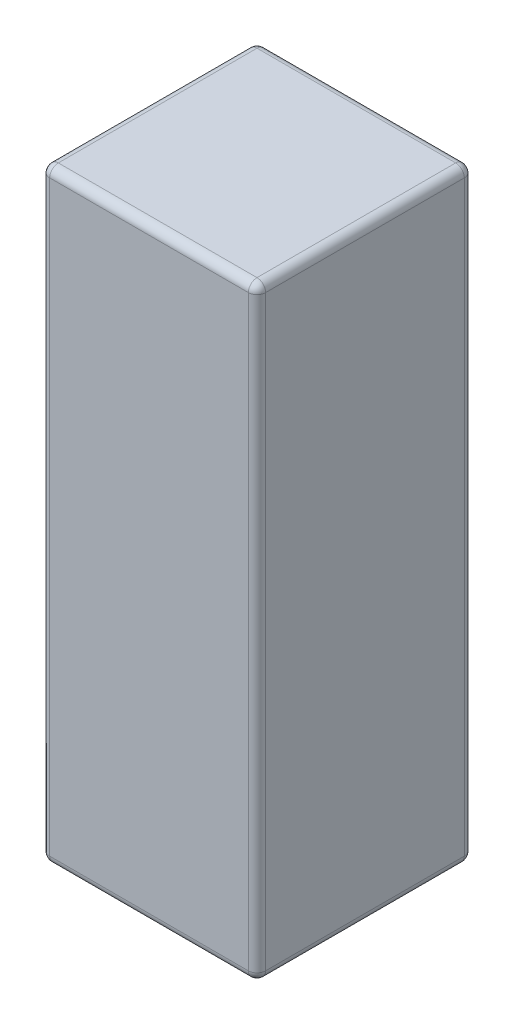
SolidWorks part; units mm, degrees
ref_plane "Front" through (0, 0, 0) normal (0, 0, 1) x (1, 0, 0)
ref_plane "Top" through (0, 0, 0) normal (0, 1, 0) x (1, 0, 0)
ref_plane "Right" through (0, 0, 0) normal (1, 0, 0) x (0, 0, -1)
sketch "Sketch1" plane through (0, 0, 0) normal (0, 1, 0) x (1, 0, 0)
  line L1 (-25, -25) -> (25, -25)
  line L2 (-25, -25) -> (-25, 25)
  line L3 (-25, 25) -> (25, 25)
  line L4 (25, -25) -> (25, 25)
  line L5 (-25, -25) -> (25, 25) construction
  line L6 (-25, 25) -> (25, -25) construction
  point P0 (0, 0)
  dimension "D1" = 50
extrude "Boss-Extrude1" add sketch "Sketch1" along normal mid plane 140
fillet "Fillet1" radius 2 8 edges at (0, -70, -25) (-25, -70, 0) (0, -70, 25) (25, -70, 0) (0, 70, 25) (-25, 70, 0) (0, 70, -25) (25, 70, 0)
fillet "Fillet2" radius 2 12 edges at (-24.4142, 69.4142, -24.4142) (-24.4142, -69.4142, -24.4142) (24.4142, 69.4142, -24.4142) (24.4142, -69.4142, -24.4142) (24.4142, 69.4142, 24.4142) (24.4142, -69.4142, 24.4142) (-24.4142, 69.4142, 24.4142) (-24.4142, -69.4142, 24.4142) (-25, 0, -25) (25, 0, -25) (25, 0, 25) (-25, 0, 25)
